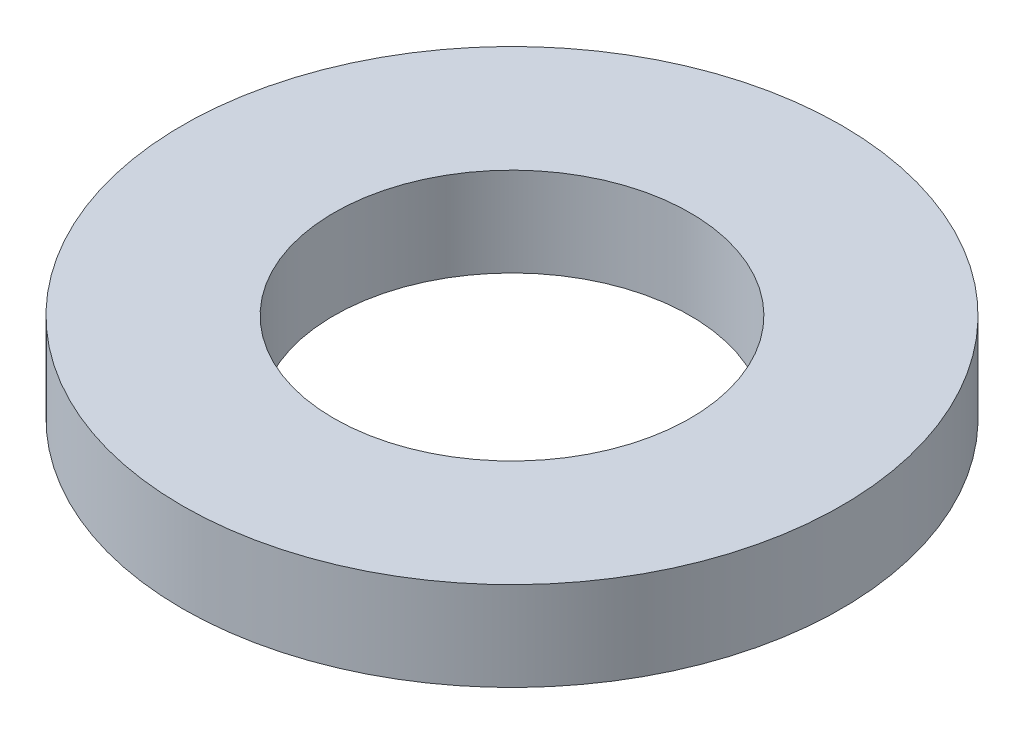
SolidWorks part; units mm, degrees
ref_plane "Front Plane" through (0, 0, 0) normal (0, 0, 1) x (1, 0, 0)
ref_plane "Top Plane" through (0, 0, 0) normal (0, 1, 0) x (1, 0, 0)
ref_plane "Right Plane" through (0, 0, 0) normal (1, 0, 0) x (0, 0, -1)
sketch "Sketch1" plane through (0, 0, 0) normal (0, 1, 0) x (1, 0, 0)
  circle A0 centre (0, 0) radius 92.5
  dimension "FLANGE_OD" = 185
extrude "Boss-Extrude1" add sketch "Sketch1" along normal blind 25
sketch "Sketch2" plane through (0, 0, 0) normal (0, 1, 0) x (1, 0, 0)
  circle A0 centre (0, 0) radius 50
  dimension "BORE_D" = 100
extrude "Cut-Extrude1" cut sketch "Sketch2" along normal through all
sketch "Sketch3" plane through (0, 25, 0) normal (0, 1, 0) x (1, 0, 0)
  circle A0 centre (0, 0) radius 37.3518 construction
  circle A1 centre (-37.3518, 0) radius 6.683
  dimension "BOLT_D" = 13.3659
  dimension "BOLT_PCD" = 74.7035
extrude "Cut-Extrude2" cut sketch "Sketch3" against normal blind 19.7242 rebuild error yes
pattern_circular "CirPattern1" count 4 over 360 rebuild error yes
